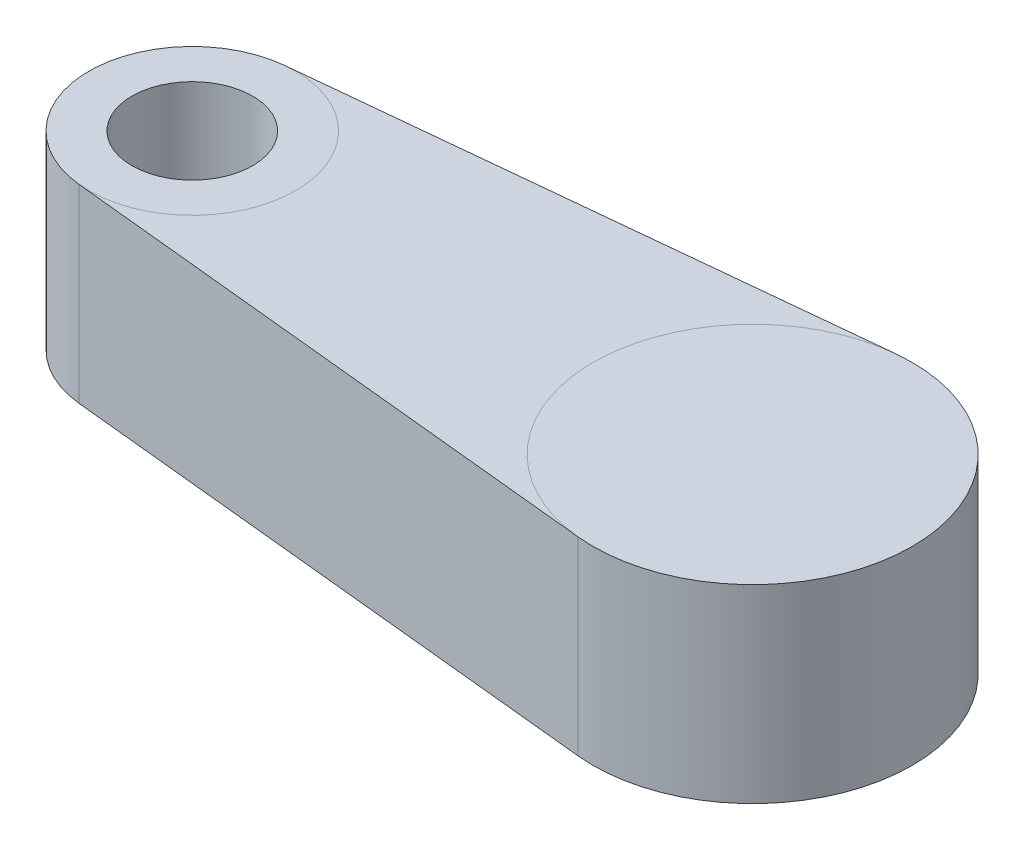
SolidWorks part; units mm, degrees
ref_plane "Front Plane" through (0, 0, 0) normal (0, 0, 1) x (1, 0, 0)
ref_plane "Top Plane" through (0, 0, 0) normal (0, 1, 0) x (1, 0, 0)
ref_plane "Right Plane" through (0, 0, 0) normal (1, 0, 0) x (0, 0, -1)
sketch "Sketch2" plane through (0, 0, 0) normal (0, 1, 0) x (1, 0, 0)
  line L0 (-103.1875, 0) -> (103.1875, 0) construction
  line L1 (0, -33.5724) -> (0, 19.05) construction
  line L2 (20.2812, 0) -> (125.5187, 0) construction
  line L3 (-1.905, -18.9545) -> (100.2506, -29.2215)
  line L4 (-1.905, 18.9545) -> (100.2506, 29.2215)
  circle A0 centre (103.1875, 0) radius 29.3688
  circle A1 centre (0, 0) radius 19.05
  circle A2 centre (0, 0) radius 11.1125
  point P5 (0, 0)
  dimension "D1" = 58.7375
  dimension "D3" = 22.225
  dimension "D4" = 38.1
  dimension "D2" = 103.1875
extrude "Boss-Extrude1" add sketch "Sketch2" along normal blind 34.925 contours A1 L3 A0 L4 | A0 | A1 region at (48.4192, 0, 0) region at (103.1875, 0, 0)
split line "Split Line4"
sketch "Sketch2<5>" plane through (0, 0, 0) normal (0, 1, 0) x (1, 0, 0) same geometry as "Sketch2"
sketch "Sketch4" plane through (0, 34.925, 0) normal (0, 1, 0) x (1, 0, 0)
  circle A0 centre (103.1875, 0) radius 19.05
  circle A1 centre (103.1875, 0) radius 29.3688 construction
  circle A2 centre (103.1875, 0) radius 29.3688
  arc A5 (100.2506, 29.2215) -> (100.2506, -29.2215) centre (103.1875, 0) ccw
  arc A6 (100.2506, -29.2215) -> (100.2506, 29.2215) centre (103.1875, 0) ccw
  arc A7 (100.2506, 29.2215) -> (100.2506, -29.2215) centre (103.1875, 0) ccw
  arc A8 (100.2506, -29.2215) -> (100.2506, 29.2215) centre (103.1875, 0) ccw
  dimension "D1" = 38.1
  dimension "D2" = 0
extrude "Cut-Extrude1" cut sketch "Sketch4" against normal through all rebuild error yes
extrude "Cut-Extrude2" cut sketch "Sketch2<6>" along normal blind 34.925 contours A2
sketch "Sketch2<6>" plane through (0, 0, 0) normal (0, 1, 0) x (1, 0, 0) same geometry as "Sketch2"
